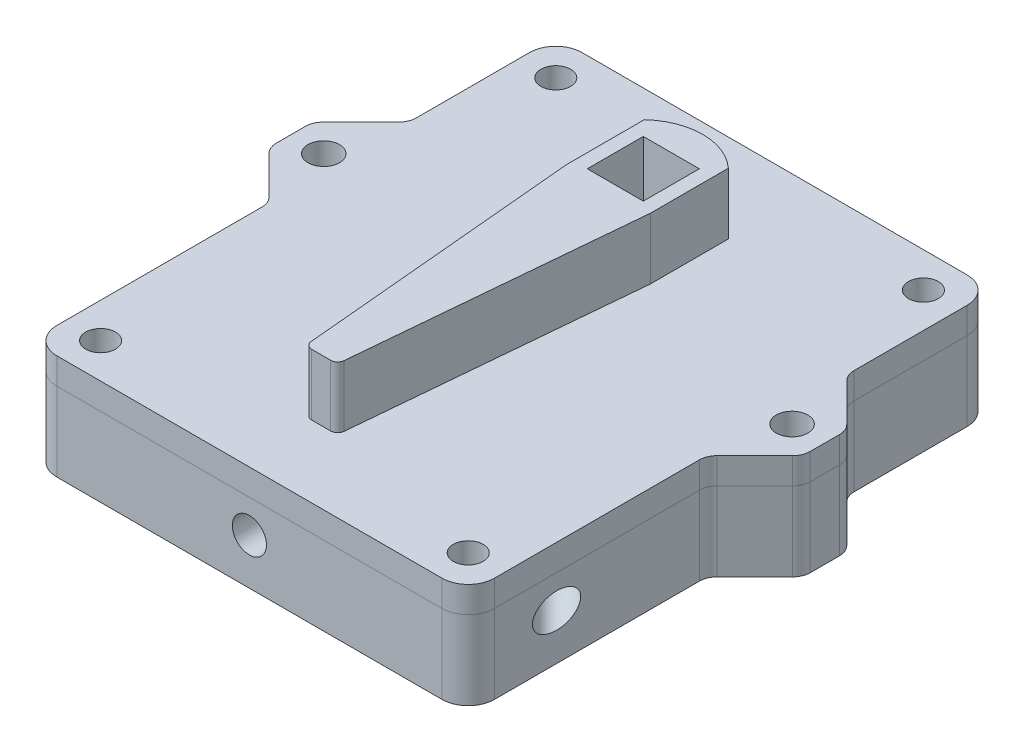
SolidWorks part; units mm, degrees
note: The reader was unsure of these and kept them because the rebuilt part matched: shared geometry of "Sketch33<3>".
ref_plane "Front Plane" through (0, 0, 0) normal (0, 0, 1) x (1, 0, 0)
ref_plane "Top Plane" through (0, 0, 0) normal (0, 1, 0) x (1, 0, 0)
ref_plane "Right Plane" through (0, 0, 0) normal (1, 0, 0) x (0, 0, -1)
other "Center of Mass"
sketch "Sketch1" plane through (0, 0, 0) normal (0, 1, 0) x (1, 0, 0)
  line L1 (-25, -30) -> (25, -30)
  line L2 (-25, -30) -> (-25, 30)
  line L3 (-25, 30) -> (25, 30)
  line L4 (25, -30) -> (25, 30)
  line L5 (-25, -30) -> (25, 30) construction
  line L6 (-25, 30) -> (25, -30) construction
  point P0 (0, 0)
  dimension "D1" = 50
  dimension "D2" = 60
extrude "Boss-Extrude1" add sketch "Sketch1" along normal blind 12
sketch "Sketch7" plane through (0, 12, 0) normal (0, 1, 0) x (1, 0, 0)
  line L0 (-21, 26) -> (-21, -26) construction
  line L1 (-21, 26) -> (21, 26) construction
  line L2 (-25, 30) -> (-25, -30) construction
  line L3 (25, 30) -> (-25, 30) construction
  circle A0 centre (-21, 26) radius 1.7
  circle A1 centre (21, 26) radius 1.7
  circle A2 centre (21, -26) radius 1.7
  circle A3 centre (-21, -26) radius 1.7
  point P3 (0, 26)
  point P4 (-21, 0)
  dimension "D1" = 3.4
  dimension "D4" = 4
  dimension "D5" = 4
  dimension "D2" = 2
  dimension "D3" = 2
extrude "Cut-Extrude4" cut sketch "Sketch7" against normal up to surface (12 mm away) up to face at (0, 0, 0)
fillet "Fillet2" radius 3 4 edges at (-25, 6, -30) (25, 6, -30) (25, 6, 30) (-25, 6, 30)
ref_plane "Plane1" through (0, 9, 0) normal (0, 1, 0) x (1, 0, 0)
split "Split1" trim tools "Plane1" bodies to split 110 resulting bodies 108 109
sketch "ChannelCavity" plane through (0, 9, 0) normal (0, 1, 0) x (1, 0, 0)
  line L0 (5, -22) -> (2, -22) construction
  line L2 (-5, -22) -> (-5, 11) construction
  line L15 (0, 30) -> (0, -30) construction
  line L16 (-5, 11) -> (-2, -22)
  line L17 (5, 11) -> (2, -22)
  line L22 (22, 30) -> (-22, 30) construction
  line L27 (5, -22) -> (5, 11) construction
  line L28 (-2, -22) -> (-5, -22) construction
  line L29 (2, -22) -> (-2, -22)
  line L30 (-22, -30) -> (22, -30) construction
  line L31 (-5, 11) -> (-5, 22)
  line L32 (-5, 22) -> (5, 22) construction
  line L33 (5, 22) -> (5, 11)
  line L36 (-3, 18) -> (3, 18)
  line L37 (-3, 18) -> (-3, 12)
  line L38 (-3, 12) -> (3, 12)
  line L39 (3, 18) -> (3, 12)
  line L40 (5, 22) -> (5, -22) construction
  line L42 (25, -27) -> (25, 27) construction
  arc A1 (-5, 20) -> (5, 20) centre (0, 14.75) cw
  point P20 (0, 18)
  point P23 (5, 0)
  point P26 (25, 0)
  dimension "D8" = 2
  dimension "D1" = 10
  dimension "D2" = 4
  dimension "D3" = 1
  dimension "D4" = 6
  dimension "D5" = 33
  dimension "D6" = 6
  dimension "D7" = 4
extrude "Cut-Extrude1" cut sketch "ChannelCavity" against normal offset from surface (7.5 mm away) 1.5 contours A1 L31 L16 L29 L17 L33 L36 L39 L38 L37 up to face at (-21, 0, 24.3)
ref_plane "Plane4" through (0, 5.25, 0) normal (0, 1, 0) x (1, 0, 0)
sketch "Sketch4" plane through (0, 0, 22) normal (0, 0, -1) x (-1, 0, 0)
  line L6 (27.5, 5.25) -> (-27.5, 5.25) construction
  line L7 (0, 10.45) -> (0, -10.45) construction
  circle A0 centre (0, 5.25) radius 1.95
  dimension "D1" = 3.9
extrude "Cut-Extrude3" cut sketch "Sketch4" against normal up to surface (8 mm away) up to face at (0, 4.5, 30)
sketch "Sketch9" plane through (0, 0, 0) normal (0, -1, 0) x (1, 0, 0)
  circle A0 centre (-21, 26) radius 3
  circle A1 centre (21, 26) radius 3
  circle A2 centre (21, -26) radius 3
  circle A3 centre (-21, -26) radius 3
  dimension "D1" = 6
extrude "Cut-Extrude5" cut sketch "Sketch9" against normal blind 3.4
sketch "Sketch32" plane through (0, 5.25, 0) normal (0, 1, 0) x (1, 0, 0)
  line L0 (-4.0909, 1) -> (-25, -19.9091) construction
  line L2 (-25, 27) -> (-25, -27) construction
  line L3 (-5, 11) -> (-2, -22) construction
  line L4 (-5, -22) -> (-5, 11) construction
  point P0 (-19.3431, -14.2522)
  dimension "D1" = 45
  dimension "D2" = 10
  dimension "D3" = 8
ref_plane "Plane3" through (-19.3431, 5.25, 14.2522) normal (-0.7071, 0, 0.7071) x (0.7071, 0, 0.7071)
sketch "Sketch33" plane through (-19.3431, 5.25, 14.2522) normal (-0.7071, 0, 0.7071) x (0.7071, 0, 0.7071)
  circle A0 centre (0, 0) radius 1.5
  circle A1 centre (0, 0) radius 1.95
  dimension "D1" = 3
  dimension "D2" = 3.9
extrude "Cut-Extrude12" cut sketch "Sketch33" along normal up to surface (9.95 mm away) contours A1
extrude "Cut-Extrude13" cut sketch "Sketch33<3>" against normal up to surface (20.3199 mm away) contours A0
sketch "Sketch33<3>" plane through (-19.3431, 5.25, 14.2522) normal (-0.7071, 0, 0.7071) x (0.7071, 0, 0.7071) same geometry as "Sketch33"
mirror "Mirror1" about plane through (0, 0, 0) normal (1, 0, 0) of "Cut-Extrude12", "Cut-Extrude13"
sketch "Sketch10" plane through (0, 9, 0) normal (0, 1, 0) x (1, 0, 0)
  line L0 (-23, 0) -> (-23, -18.7674)
  line L1 (-23, -18.7674) -> (-13.7674, -28)
  line L2 (-13.7674, -28) -> (0, -28)
  line L3 (0, 0) -> (-20, 0) construction
  line L5 (0, 0) -> (0, 25) construction
  line L6 (-19, 0) -> (-19, -17.1106)
  line L7 (-25, 27) -> (-25, -27) construction
  line L8 (-22, -30) -> (22, -30) construction
  line L9 (-19, -17.1106) -> (-12.1106, -24)
  line L10 (-12.1106, -24) -> (0, -24)
  line L11 (12.1106, -24) -> (0, -24)
  line L12 (19, -17.1106) -> (12.1106, -24)
  line L13 (19, 17.1106) -> (19, -17.1106)
  line L14 (13.7674, -28) -> (0, -28)
  line L15 (23, -18.7674) -> (13.7674, -28)
  line L16 (23, 18.7674) -> (23, -18.7674)
  line L17 (23, 18.7674) -> (13.7674, 28)
  line L18 (13.7674, 28) -> (0, 28)
  line L19 (19, 17.1106) -> (12.1106, 24)
  line L20 (12.1106, 24) -> (0, 24)
  line L21 (-12.1106, 24) -> (0, 24)
  line L22 (-19, 17.1106) -> (-12.1106, 24)
  line L23 (-19, 0) -> (-19, 17.1106)
  line L24 (-13.7674, 28) -> (0, 28)
  line L25 (-23, 18.7674) -> (-13.7674, 28)
  line L26 (-23, 0) -> (-23, 18.7674)
  line L27 (-12.1106, -24) -> (0.0194, -24) construction
  line L28 (-13.7674, -28) -> (0.0194, -28) construction
  point P30 (23, 0)
  point P33 (19, 0)
  dimension "D4" = 13.0569
  dimension "D1" = 2
  dimension "D2" = 2
  dimension "D3" = 135
  dimension "D5" = 4
extrude "Cut-Extrude6" cut sketch "Sketch10" against normal blind 1
fillet "Fillet5" radius 2 16 edges at (-19, 8.5, 17.1106) (-12.1106, 8.5, 24) (12.1106, 8.5, 24) (19, 8.5, 17.1106) (19, 8.5, -17.1106) (12.1106, 8.5, -24) (-19, 8.5, -17.1106) (-12.1106, 8.5, -24) (13.7674, 8.5, -28) (23, 8.5, -18.7674) (23, 8.5, 18.7674) (13.7674, 8.5, 28) (-13.7674, 8.5, 28) (-23, 8.5, 18.7674) (-13.7674, 8.5, -28) (-23, 8.5, -18.7674)
sketch "Sketch21" plane through (0, 9, 0) normal (0, 1, 0) x (1, 0, 0)
  line L1 (-25, 27) -> (-25, -27) construction
  line L5 (0, -6.6) -> (0, 6.6) construction
  line L6 (-25, 13.2426) -> (-30.5, 7.7426)
  line L7 (-30.5, 7.7426) -> (-30.5, 2.7426)
  line L9 (-25, -2.7574) -> (-25, 13.2426)
  line L10 (22, 30) -> (-22, 30) construction
  line L11 (-30.5, 2.7426) -> (-25, -2.7574)
  line L12 (-30.5, 5.2426) -> (-25, 5.2426) construction
  line L13 (30.5, 5.2426) -> (25, 5.2426) construction
  line L14 (30.5, 2.7426) -> (25, -2.7574)
  line L15 (25, -2.7574) -> (25, 13.2426)
  line L16 (30.5, 7.7426) -> (30.5, 2.7426)
  line L17 (25, 13.2426) -> (30.5, 7.7426)
  dimension "D1" = 5.5
  dimension "D2" = 5
  dimension "D3" = 45
  dimension "D4" = 24.7574
extrude "Boss-Extrude11" add sketch "Sketch21" against normal up to surface (9 mm away) up to face at (-21, 0, -29)
sketch "Sketch25" plane through (0, 9, 0) normal (0, 1, 0) x (1, 0, 0)
  line L0 (-30.5, 5.2426) -> (-23, 5.2426) construction
  line L1 (-30.5, 7.7426) -> (-30.5, 2.7426) construction
  line L3 (0, -6.6) -> (0, 6.6) construction
  line L4 (-23, 17.939) -> (-23, -17.939) construction
  circle A0 centre (-26.75, 5.2426) radius 1.8
  circle A1 centre (26.75, 5.2426) radius 1.8
  dimension "D1" = 3.6
extrude "Cut-Extrude7" cut sketch "Sketch25" against normal up to surface (9 mm away) up to face at (-21, 0, -29)
sketch "Sketch26" plane through (0, 0, 0) normal (0, -1, 0) x (1, 0, 0)
  circle A0 centre (-26.75, -5.2426) radius 3
  circle A1 centre (26.75, -5.2426) radius 3
  circle A2 centre (-21, 26) radius 3 construction
extrude "Cut-Extrude9" cut sketch "Sketch26" against normal blind 3.4
fillet "Fillet6" radius 2 8 edges at (-25, 4.5, -13.2426) (-30.5, 4.5, -7.7426) (-30.5, 4.5, -2.7426) (-25, 4.5, 2.7574) (25, 4.5, -13.2426) (30.5, 4.5, -7.7426) (30.5, 4.5, -2.7426) (25, 4.5, 2.7574)
sketch "Sketch29" plane through (0, 9, 0) normal (0, -1, 0) x (1, 0, 0)
  line L0 (25.5858, 2.1716) -> (29.9142, -2.1569) construction
  line L1 (30.5, -3.5711) -> (30.5, -6.9142) construction
  line L2 (29.9142, -8.3284) -> (25.5858, -12.6569) construction
  line L3 (-29.9142, -2.1569) -> (-25.5858, 2.1716) construction
  line L4 (-30.5, -6.9142) -> (-30.5, -3.5711) construction
  line L5 (-25.5858, -12.6569) -> (-29.9142, -8.3284) construction
  line L6 (25.5858, 2.1716) -> (29.9142, -2.1569)
  line L7 (30.5, -3.5711) -> (30.5, -6.9142)
  line L8 (29.9142, -8.3284) -> (25.5858, -12.6569)
  line L9 (-29.9142, -2.1569) -> (-25.5858, 2.1716)
  line L10 (-30.5, -6.9142) -> (-30.5, -3.5711)
  line L11 (-25.5858, -12.6569) -> (-29.9142, -8.3284)
  line L12 (-25, -14.0711) -> (-25, 3.5858)
  line L13 (25, -14.0711) -> (25, 3.5858)
  arc A0 (25, 3.5858) -> (25.5858, 2.1716) centre (27, 3.5858) ccw construction
  arc A1 (30.5, -3.5711) -> (29.9142, -2.1569) centre (28.5, -3.5711) ccw construction
  arc A2 (29.9142, -8.3284) -> (30.5, -6.9142) centre (28.5, -6.9142) ccw construction
  arc A3 (25.5858, -12.6569) -> (25, -14.0711) centre (27, -14.0711) ccw construction
  arc A4 (-25.5858, 2.1716) -> (-25, 3.5858) centre (-27, 3.5858) ccw construction
  arc A5 (-29.9142, -2.1569) -> (-30.5, -3.5711) centre (-28.5, -3.5711) ccw construction
  arc A6 (-30.5, -6.9142) -> (-29.9142, -8.3284) centre (-28.5, -6.9142) ccw construction
  arc A7 (-25, -14.0711) -> (-25.5858, -12.6569) centre (-27, -14.0711) ccw construction
  arc A8 (25, 3.5858) -> (25.5858, 2.1716) centre (27, 3.5858) ccw
  arc A9 (30.5, -3.5711) -> (29.9142, -2.1569) centre (28.5, -3.5711) ccw
  arc A10 (29.9142, -8.3284) -> (30.5, -6.9142) centre (28.5, -6.9142) ccw
  arc A11 (25.5858, -12.6569) -> (25, -14.0711) centre (27, -14.0711) ccw
  arc A12 (-25.5858, 2.1716) -> (-25, 3.5858) centre (-27, 3.5858) ccw
  arc A13 (-29.9142, -2.1569) -> (-30.5, -3.5711) centre (-28.5, -3.5711) ccw
  arc A14 (-30.5, -6.9142) -> (-29.9142, -8.3284) centre (-28.5, -6.9142) ccw
  arc A15 (-25, -14.0711) -> (-25.5858, -12.6569) centre (-27, -14.0711) ccw
extrude "Boss-Extrude13" add sketch "Sketch29" against normal up to surface (3 mm away)
sketch "Sketch30" plane through (0, 12, 0) normal (0, 1, 0) x (1, 0, 0)
  circle A4 centre (-26.75, 5.2426) radius 1.8 construction
  circle A5 centre (26.75, 5.2426) radius 1.8 construction
  circle A6 centre (-26.75, 5.2426) radius 1.8
  circle A7 centre (26.75, 5.2426) radius 1.8
extrude "Cut-Extrude11" cut sketch "Sketch30" against normal up to surface (3 mm away)
sketch "Sketch31" plane through (0, 0, 22) normal (0, 0, -1) x (-1, 0, 0)
  circle A0 centre (0, 5.25) radius 1.95 construction
  circle A1 centre (0, 5.25) radius 1.95
  circle A2 centre (0, 5.25) radius 1.5
  dimension "D1" = 3
extrude "Boss-Extrude14" add sketch "Sketch31" against normal blind 1
fillet "Fillet7" radius 1 2 edges at (-2, 5.25, 22) (2, 5.25, 22)
sketch "Sketch39" plane through (0, 9, 0) normal (0, 1, 0) x (1, 0, 0)
  line L6 (-4.8, 11.0091) -> (-1.8835, -21.0724)
  line L7 (-1.0868, -21.8) -> (1.0868, -21.8)
  line L8 (3, 12) -> (3, 18)
  line L9 (3, 18) -> (-3, 18)
  line L10 (-3, 18) -> (-3, 12)
  line L11 (-3, 12) -> (3, 12)
  line L12 (3, 12) -> (3, 18) construction
  line L13 (3, 18) -> (-3, 18) construction
  line L14 (-3, 18) -> (-3, 12) construction
  line L15 (-3, 12) -> (3, 12) construction
  line L22 (-5, 11) -> (-2.0827, -21.0905)
  line L23 (-1.0868, -22) -> (1.0868, -22)
  line L24 (2.0827, -21.0905) -> (5, 11)
  line L25 (5, 11) -> (5, 20)
  line L26 (-5, 20) -> (-5, 11)
  line L27 (-5, 11) -> (-2.0827, -21.0905) construction
  line L28 (-1.0868, -22) -> (1.0868, -22) construction
  line L29 (2.0827, -21.0905) -> (5, 11) construction
  line L30 (5, 11) -> (5, 20) construction
  line L31 (-5, 20) -> (-5, 11) construction
  line L32 (1.8835, -21.0724) -> (4.8, 11.0091)
  line L33 (4.8, 11.0091) -> (4.8, 19.9136)
  line L34 (-4.8, 19.9136) -> (-4.8, 11.0091)
  line L35 (-3.2, 18.2) -> (-3.2, 11.8)
  line L36 (-3.2, 11.8) -> (3.2, 11.8)
  line L37 (3.2, 11.8) -> (3.2, 18.2)
  line L38 (3.2, 18.2) -> (-3.2, 18.2)
  arc A2 (-1.8835, -21.0724) -> (-1.0868, -21.8) centre (-1.0868, -21) ccw
  arc A3 (1.0868, -21.8) -> (1.8835, -21.0724) centre (1.0868, -21) ccw
  arc A5 (-2.0827, -21.0905) -> (-1.0868, -22) centre (-1.0868, -21) ccw
  arc A6 (1.0868, -22) -> (2.0827, -21.0905) centre (1.0868, -21) ccw
  arc A7 (5, 20) -> (-5, 20) centre (0, 14.75) ccw
  arc A8 (-2.0827, -21.0905) -> (-1.0868, -22) centre (-1.0868, -21) ccw construction
  arc A9 (1.0868, -22) -> (2.0827, -21.0905) centre (1.0868, -21) ccw construction
  arc A10 (5, 20) -> (-5, 20) centre (0, 14.75) ccw construction
  arc A11 (4.8, 19.9136) -> (-4.8, 19.9136) centre (0, 14.75) ccw
  dimension "D1" = 0
  dimension "D2" = 0
  dimension "D3" = 0.2
  dimension "D4" = 0.2
extrude "Boss-Extrude17" add sketch "Sketch39" along normal blind 10 separate body
chamfer "Chamfer1" distance 1 angle 45 1 edges at (0, 9, -22)
sketch "Sketch40" plane through (0, 9, 0) normal (0, 1, 0) x (1, 0, 0)
  line L0 (11.2821, 24) -> (-11.2821, 24) construction
  line L1 (-7.2614, 24) -> (7.2614, 24)
  line L2 (-7.2614, 24) -> (-7.2614, -24)
  line L3 (-7.2614, -24) -> (7.2614, -24)
  line L4 (7.2614, 24) -> (7.2614, -24)
  line L5 (-11.2821, -24) -> (11.2821, -24) construction
  line L6 (-11.2821, -24) -> (11.2821, -24) construction
  line L8 (-43.0088, 36.0866) -> (50.8545, 36.0866)
  line L9 (-43.0088, 36.0866) -> (-43.0088, -44.33)
  line L10 (-43.0088, -44.33) -> (50.8545, -44.33)
  line L11 (50.8545, 36.0866) -> (50.8545, -44.33)
  point P8 (0, -24)
  point P11 (0, -24)
extrude "Cut-Extrude14" [suppressed] cut sketch "Sketch40" against normal through all
equation "\"ANGLE\"=45"
equation "\"CORRIDOR_LENGTH\"=40"
